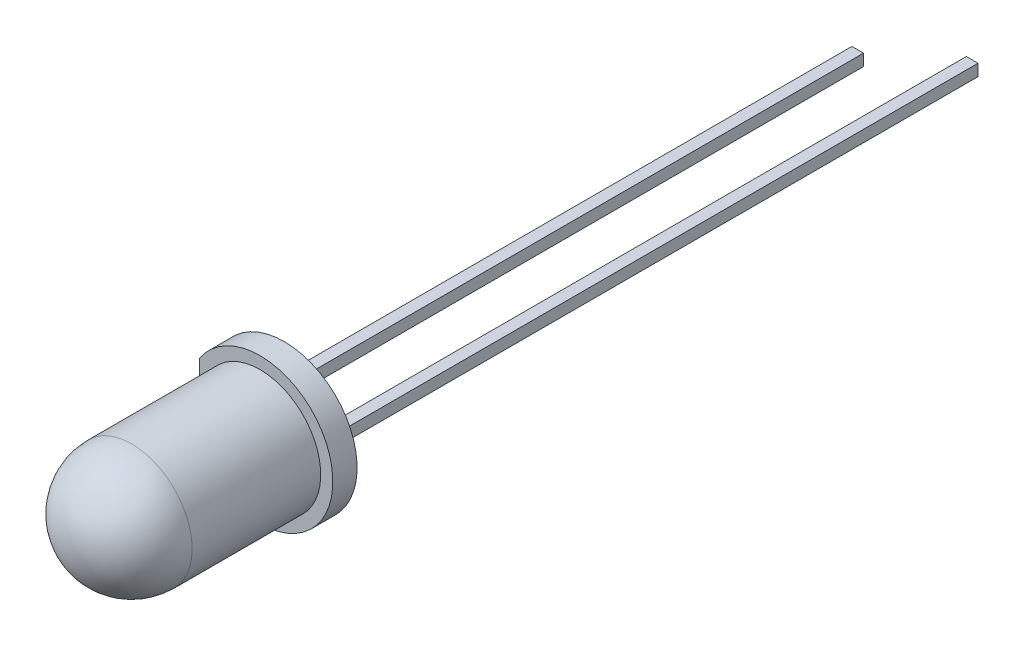
SolidWorks part; units mm, degrees
ref_plane "Plano frontal" through (0, 0, 0) normal (0, 0, 1) x (1, 0, 0)
ref_plane "Plano superior" through (0, 0, 0) normal (0, 1, 0) x (1, 0, 0)
ref_plane "Plano direito" through (0, 0, 0) normal (1, 0, 0) x (0, 0, -1)
sketch "Esboço1" plane through (0, 0, 0) normal (0, 0, 1) x (1, 0, 0)
  circle A0 centre (0, 0) radius 3
  dimension "D1" = 6
extrude "Ressalto-extrusão1" add sketch "Esboço1" along normal blind 1
sketch "Esboço3" plane through (0, 0, 0) normal (1, 0, 0) x (0, 0, -1)
  line L0 (-1, 0) -> (-8.8, 0)
  line L1 (-1, 3) -> (-1, -3) construction
  line L2 (-6.3, 2.5) -> (-1, 2.5)
  line L3 (-1, 0) -> (-1, 2.5)
  arc A0 (-8.8, 0) -> (-6.3, 2.5) centre (-6.3, 0) cw
  dimension "D1" = 2.5
  dimension "D2" = 7.8
revolve "Revolução1" add sketch "Esboço3" angle 360 about L0
sketch "Esboço4" plane through (0, 0, 0) normal (0, 0, -1) x (-1, 0, 0)
  line L0 (2.5, 1.6583) -> (2.5, -1.6583)
  circle A0 centre (0, 0) radius 3 construction
  arc A1 (2.5, -1.6583) -> (2.5, 1.6583) centre (0, 0) ccw
  circle A2 centre (0, 0) radius 2.5 construction
extrude "Corte-extrusão1" cut sketch "Esboço4" against normal up to surface (1 mm away) up to face at (2.5, 0, 1)
sketch "Esboço5" plane through (0, 0, 0) normal (0, 0, -1) x (-1, 0, 0)
  line L0 (-1.12, 0) -> (1.12, 0) construction
  line L1 (-1.6, -0.24) -> (-1.12, -0.24)
  line L2 (-1.6, -0.24) -> (-1.6, 0.24)
  line L3 (-1.6, 0.24) -> (-1.12, 0.24)
  line L4 (-1.12, -0.24) -> (-1.12, 0.24)
  line L5 (1.12, -0.24) -> (1.6, -0.24)
  line L6 (1.12, -0.24) -> (1.12, 0.24)
  line L7 (1.12, 0.24) -> (1.6, 0.24)
  line L8 (1.6, -0.24) -> (1.6, 0.24)
  dimension "D1" = 3.2
  dimension "D2" = 0.48
extrude "Ressalto-extrusão2" add sketch "Esboço5" along normal blind 25 separate body
sketch "Esboço6" plane through (0, 0, -25) normal (0, 0, -1) x (-1, 0, 0)
  line L4 (-1.6, 0.24) -> (-1.6, -0.24)
  line L5 (-1.6, -0.24) -> (-1.12, -0.24)
  line L6 (-1.12, -0.24) -> (-1.12, 0.24)
  line L7 (-1.12, 0.24) -> (-1.6, 0.24)
  line L8 (-1.6, 0.24) -> (-1.6, -0.24)
  line L9 (-1.6, -0.24) -> (-1.12, -0.24)
  line L10 (-1.12, -0.24) -> (-1.12, 0.24)
  line L11 (-1.12, 0.24) -> (-1.6, 0.24)
  dimension "D1" = 0
extrude "Ressalto-extrusão3" add sketch "Esboço6" along normal blind 2 separate body
sketch "Esboço7" plane through (0, 0, 0) normal (0, 1, 0) x (1, 0, 0)
  line L0 (-1.6, 0) -> (-1.6, -3.5)
  line L1 (-1.12, 0) -> (-1.12, -2)
  line L2 (0.02, -2) -> (1.2, -4)
  line L3 (1.2, -4) -> (-1.3, -4)
  line L4 (-1.3, -4) -> (-1.6, -3.5)
  line L5 (-1.12, -2) -> (0.02, -2)
  line L6 (1.6, 0) -> (1.6, -4)
  line L7 (1.6, -4) -> (1.4, -4)
  line L8 (1.4, -4) -> (0.22, -2)
  line L9 (0.22, -2) -> (1.12, -2)
  line L10 (1.12, -2) -> (1.12, 0)
  line L11 (-1.6, 0) -> (-1.12, 0)
  line L12 (1.12, 0) -> (1.6, 0)
  dimension "D1" = 4
  dimension "D2" = 2
  dimension "D3" = 2.8
  dimension "D4" = 0.2
  dimension "D5" = 0.9
  dimension "D6" = 3.5
  dimension "D7" = 2.5
extrude "Corte-extrusão2" cut sketch "Esboço7" against normal mid plane 0.48
sketch "Esboço8" plane through (0, 0, 0) normal (0, 1, 0) x (1, 0, 0)
  line L0 (-1.3, -4) -> (1.2, -4) construction
  line L1 (-1.6, -3.5) -> (-1.3, -4) construction
  line L2 (-1.6, 0) -> (-1.6, -3.5) construction
  line L3 (1.2, -4) -> (0.02, -2) construction
  line L4 (0.02, -2) -> (-1.12, -2) construction
  line L5 (-1.12, -2) -> (-1.12, 0) construction
  line L6 (0.22, -2) -> (1.4, -4) construction
  line L7 (1.12, -2) -> (0.22, -2) construction
  line L8 (1.12, 0) -> (1.12, -2) construction
  line L9 (1.6, -4) -> (1.6, 0) construction
  line L10 (1.4, -4) -> (1.6, -4) construction
  line L11 (-1.12, 0) -> (-1.6, 0) construction
  line L12 (1.6, 0) -> (1.12, 0) construction
  line L13 (-1.3, -4) -> (1.2, -4)
  line L14 (-1.6, -3.5) -> (-1.3, -4)
  line L15 (-1.6, 0) -> (-1.6, -3.5)
  line L16 (1.2, -4) -> (0.02, -2)
  line L17 (0.02, -2) -> (-1.12, -2)
  line L18 (-1.12, -2) -> (-1.12, 0)
  line L19 (0.22, -2) -> (1.4, -4)
  line L20 (1.12, -2) -> (0.22, -2)
  line L21 (1.12, 0) -> (1.12, -2)
  line L22 (1.6, -4) -> (1.6, 0)
  line L23 (1.4, -4) -> (1.6, -4)
  line L24 (-1.12, 0) -> (-1.6, 0)
  line L25 (1.6, 0) -> (1.12, 0)
extrude "Ressalto-extrusão4" add sketch "Esboço8" along normal mid plane 0.48 separate body
combine bodies "Combinar1" operation type add bodies to combine 109 106 104
combine bodies "Combinar2" operation type add bodies to combine 108 105
sketch "Esboço10" plane through (0, 0, 0) normal (0, 1, 0) x (1, 0, 0)
  line L0 (-0.05, -4) -> (-0.05, -3.7)
  line L1 (-1.3, -4) -> (1.2, -4) construction
  line L2 (-0.55, -4) -> (-0.05, -4)
  arc A0 (-0.05, -3.7) -> (-0.55, -4) centre (-0.05, -4.2667) ccw
  dimension "D1" = 0.5
  dimension "D2" = 0.3
revolve "Corte-Revolução1" cut sketch "Esboço10" angle 360 about L0
sketch "Esboço11" plane through (0, 0, 0) normal (0, 1, 0) x (1, 0, 0)
  line L0 (-0.55, -4) -> (-0.05, -4) construction
  line L1 (-0.05, -4) -> (-0.05, -3.7) construction
  line L2 (-0.55, -4) -> (-0.05, -4)
  line L3 (-0.05, -4) -> (-0.05, -3.7)
  arc A0 (-0.05, -3.7) -> (-0.55, -4) centre (-0.05, -4.2667) ccw construction
  arc A1 (-0.05, -3.7) -> (-0.55, -4) centre (-0.05, -4.2667) ccw
revolve "Revolução2" add sketch "Esboço11" angle 360 about L3
combine bodies "Combinar3" operation type add bodies to combine 113 112
sketch "Esboço12" plane through (0, 0, 4) normal (0, 0, 1) x (1, 0, 0)
  circle A0 centre (-0.05, 0) radius 0.2
  arc A1 (0.3886, 0.24) -> (-0.4886, 0.24) centre (-0.05, 0) ccw construction
  dimension "D1" = 0.4
extrude "Corte-extrusão3" cut sketch "Esboço12" against normal blind 0.1
sketch "Esboço13" plane through (0, 0, 0) normal (0, 1, 0) x (1, 0, 0)
  line L0 (1.6, 27) -> (-7.0603, 32)
  line L1 (1.6, 27) -> (1.12, 27) construction
  dimension "D1" = 10
  dimension "D2" = 30
ref_plane "Plano1" through (12.0913, 0, -20.9428) normal (0.5, 0, -0.866) x (-0.866, 0, -0.5)
